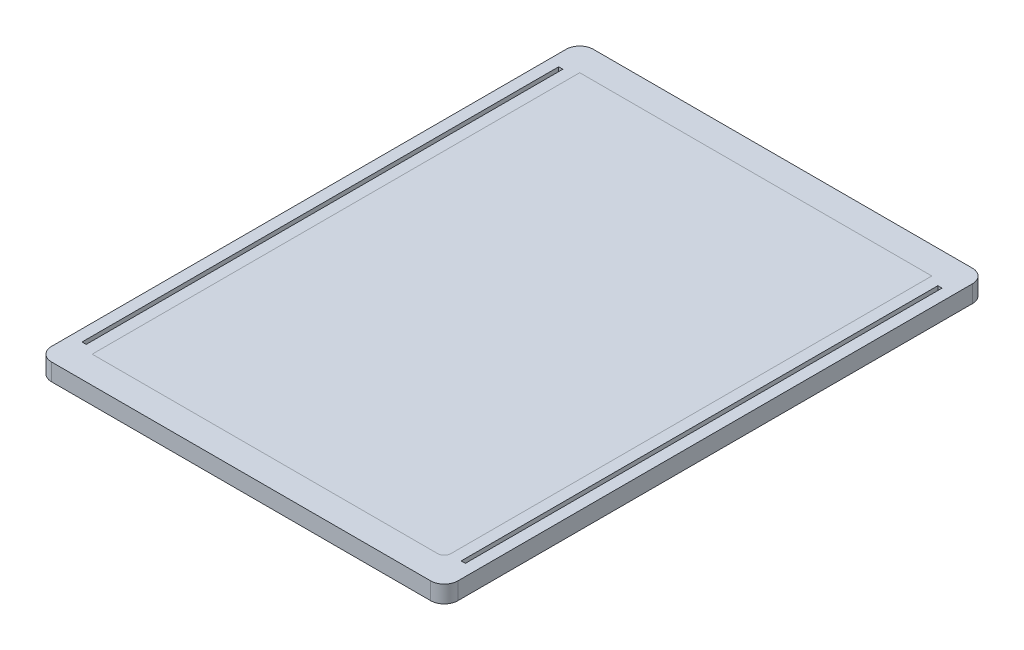
SolidWorks part; units mm, degrees
ref_plane "Front Plane" through (0, 0, 0) normal (0, 0, 1) x (1, 0, 0)
ref_plane "Top Plane" through (0, 0, 0) normal (0, 1, 0) x (1, 0, 0)
ref_plane "Right Plane" through (0, 0, 0) normal (1, 0, 0) x (0, 0, -1)
sketch "Sketch1" plane through (0, 0, 0) normal (0, 1, 0) x (1, 0, 0)
  line L0 (-65, 90) -> (65, 90)
  line L5 (-75, -100) -> (75, -100)
  line L6 (-75, -100) -> (-75, 100)
  line L7 (-75, 100) -> (75, 100)
  line L8 (75, -100) -> (75, 100)
  line L9 (-75, -100) -> (75, 100) construction
  line L10 (-75, 100) -> (75, -100) construction
  line L11 (65, -90) -> (65, 90)
  line L12 (-65, -90) -> (65, -90)
  line L13 (-65, -90) -> (-65, 90)
  line L32 (0, 100) -> (0, -100) construction
  point P0 (0, 0)
  dimension "D2" = 150
  dimension "D3" = 200
  dimension "D1" = 10
extrude "MainBody" add sketch "Sketch1" along normal mid plane 6.35
sketch "Sketch2" plane through (0, 3.175, 0) normal (0, 1, 0) x (1, 0, 0)
  line L0 (-65, 88) -> (-75, 88) construction
  line L4 (-65, 90) -> (-65, -90) construction
  line L10 (-75, 100) -> (-75, -100) construction
  line L11 (-70, 88) -> (-70, 0) construction
  line L12 (65, 90) -> (-65, 90) construction
  line L13 (75, 100) -> (-75, 100) construction
  line L18 (0, 0) -> (0, 100) construction
  line L27 (-70.7779, -88) -> (-69.2221, -88)
  line L28 (-70.7779, -88) -> (-70.7779, 88)
  line L29 (-70.7779, 88) -> (-69.2221, 88)
  line L30 (-69.2221, -88) -> (-69.2221, 88)
  line L31 (-70.7779, -88) -> (-69.2221, 88) construction
  line L32 (-70.7779, 88) -> (-69.2221, -88) construction
  dimension "D1" = 2
  dimension "D2" = 1.5557
extrude "SheetLock" cut sketch "Sketch2" against normal up to next
mirror "Mirror1" about plane through (0, 0, 0) normal (1, 0, 0) of "SheetLock"
sketch "Sketch3" plane through (0, 3.175, 0) normal (0, 1, 0) x (1, 0, 0)
  line L0 (0, 100) -> (0, -100) construction
  line L1 (75, 100) -> (-75, 100) construction
  line L2 (-75, -100) -> (75, -100) construction
  line L3 (-75, 0) -> (75, 0) construction
  line L4 (-75, 100) -> (-75, -100) construction
  line L5 (75, -100) -> (75, 100) construction
  line L6 (-65, 90) -> (-65, 100) construction
  line L7 (-65, 90) -> (-75, 90) construction
  circle A0 centre (-70, 95) radius 1.5
  circle A1 centre (70, 95) radius 1.5
  circle A2 centre (70, -95) radius 1.5
  circle A3 centre (-70, -95) radius 1.5
  point P19 (-65, 95)
  point P20 (-70, 90)
  dimension "D1" = 3
extrude "SupportHoles" [suppressed] cut sketch "Sketch3" against normal up to next
sketch "Sketch4" plane through (65, 0, 0) normal (-1, 0, 0) x (0, 0, 1)
  line L4 (-90, -3.175) -> (90, -3.175)
  line L5 (90, -3.175) -> (90, 3.175)
  line L6 (90, 3.175) -> (-90, 3.175)
  line L7 (-90, 3.175) -> (-90, -3.175)
  line L8 (-90, -3.175) -> (90, -3.175)
  line L9 (90, -3.175) -> (90, 3.175)
  line L10 (90, 3.175) -> (-90, 3.175)
  line L11 (-90, 3.175) -> (-90, -3.175)
  dimension "D1" = 0
extrude "Boss-Extrude1" add sketch "Sketch4" along normal up to surface (130 mm away) separate body up to face at (-65, 0, 0)
fillet "Fillet1" radius 5 4 edges at (-75, 0, -100) (-75, 0, 100) (75, 0, 100) (75, 0, -100)
fillet "Fillet2" radius 2.5 4 edges at (-65, 0, 90) (65, 0, 90) (65, 0, -90) (-65, 0, -90)
equation "\"SheetLockLengthOffset\"=2"
equation "\"SheetThickness\"=0.79375"
equation "\"SheetThicknessTolerance\"= 0.015in"
equation "\"LowerBasketWidth\"=150"
equation "\"D2@Sketch1\"=\"LowerBasketWidth\""
equation "\"LowerBasketLength\"=200"
equation "\"D3@Sketch1\"=\"LowerBasketLength\""
equation "\"SupportHoleDiameter\"=3"
equation "\"D1@Sketch3\"=\"SupportHoleDiameter\""
equation "\"InnerGapOffset\"=10"
equation "\"D1@Sketch1\"=\"InnerGapOffset\""
equation "\"D1@Sketch2\"=\"SheetLockLengthOffset\""
equation "\"D2@Sketch2\"=\"SheetThickness\" + \"SheetThicknessTolerance\"*2"
